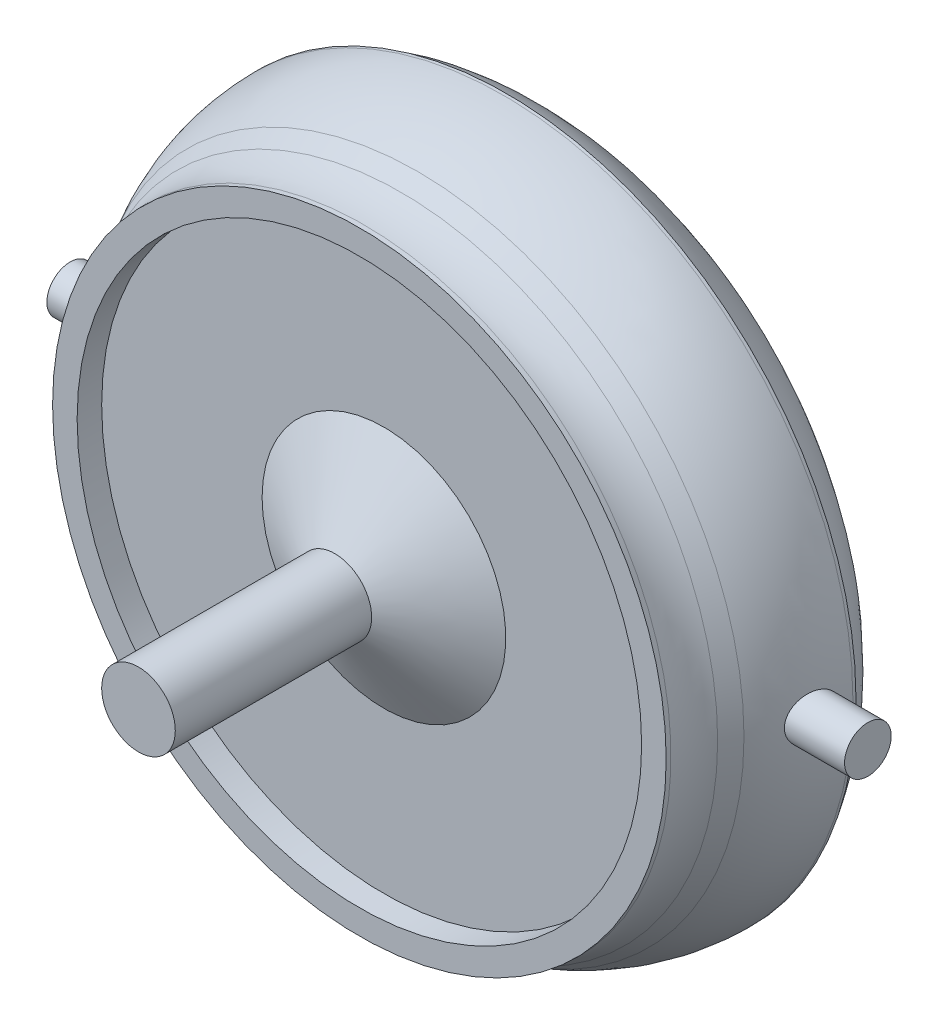
SolidWorks part; units mm, degrees
ref_plane "Front Plane" through (0, 0, 0) normal (0, 0, 1) x (1, 0, 0)
ref_plane "Top Plane" through (0, 0, 0) normal (0, 1, 0) x (1, 0, 0)
ref_plane "Right Plane" through (0, 0, 0) normal (1, 0, 0) x (0, 0, -1)
sketch "Sketch1" plane through (0, 0, 0) normal (0, 0, 1) x (1, 0, 0)
  circle A0 centre (0, 0) radius 15
extrude "Boss-Extrude1" add sketch "Sketch1" along normal blind 80
sketch "Sketch2" plane through (0, 0, 0) normal (0, 0, -1) x (-1, 0, 0)
  circle A0 centre (0, 0) radius 15
extrude "Boss-Extrude2" add sketch "Sketch2" along normal blind 20 draft 60 draft outward yes
sketch "Sketch3" plane through (0, 0, -20) normal (0, 0, -1) x (-1, 0, 0)
  circle A0 centre (0, 0) radius 125
extrude "Boss-Extrude5" add sketch "Sketch3" along normal blind 30 draft 30 draft outward yes
sketch "Sketch6" plane through (0, 0, -20) normal (0, 0, 1) x (1, 0, 0)
  circle A0 centre (0, 0) radius 125
  circle A1 centre (0, 0) radius 115
extrude "Boss-Extrude6" add sketch "Sketch6" along normal blind 10
sketch "Sketch7" plane through (0, 0, -50) normal (0, 0, -1) x (-1, 0, 0)
  circle A0 centre (0, 0) radius 142.3205
  circle A1 centre (0, 0) radius 142.3205 construction
extrude "Boss-Extrude7" add sketch "Sketch7" along normal blind 20
sketch "Sketch9" plane through (0, 0, -70) normal (0, 0, -1) x (-1, 0, 0)
  circle A0 centre (0, 0) radius 142.3205
  circle A1 centre (0, 0) radius 142.3205 construction
extrude "Boss-Extrude8" add sketch "Sketch9" along normal blind 30 draft 30
ref_plane "Plane3" through (-142.3205, 0, 0) normal (-1, 0, 0) x (0, 0, 1)
fillet "Fillet1" radius 60 1 edges at (-125, 0, -100) type face fillet first side face at (-125, 0, -100) second side face at (-125, 0, -100)
fillet "Fillet3" radius 70 1 edges at (-142.3205, 0, -50) type face fillet first side face at (-142.3205, 0, -70) second side face at (-142.3205, 0, -50)
fillet "Fillet4" radius 30 1 edges at (125, 0, -20) type face fillet first side face at (132.9423, 0, -33.7564) second side face at (125, 0, -10)
sketch "Sketch10" plane through (-142.3205, 0, 0) normal (-1, 0, 0) x (0, 0, 1)
  circle A1 centre (-54.4902, 0) radius 9.5
extrude "Boss-Extrude9" add sketch "Sketch10" along normal blind 20 and the other way blind 305
